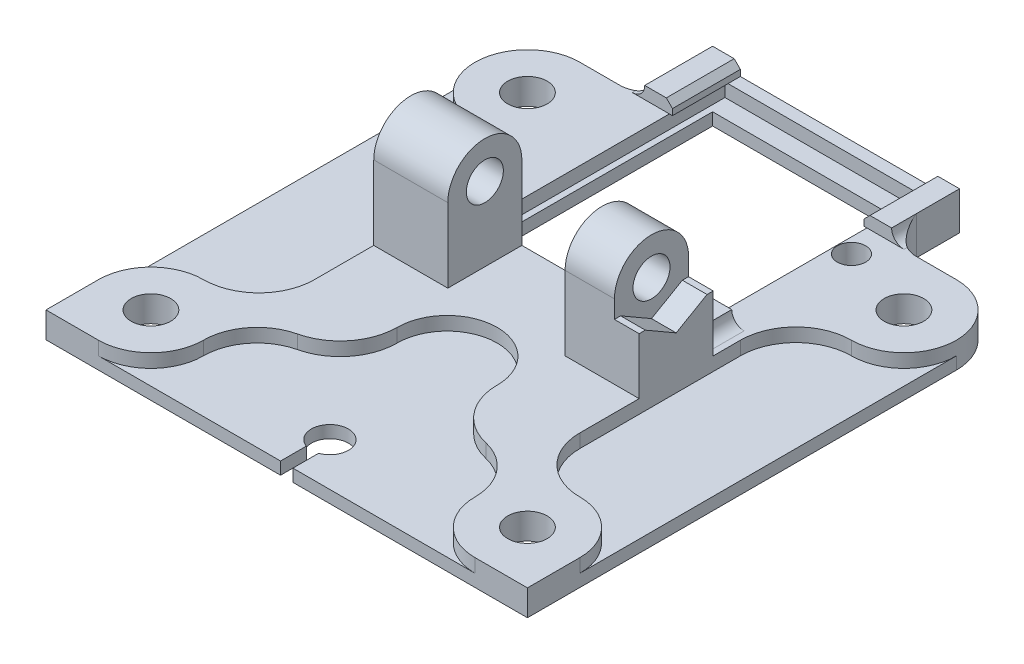
SolidWorks part; units mm, degrees
ref_plane "Front Plane" through (0, 0, 0) normal (0, 0, 1) x (1, 0, 0)
ref_plane "Top Plane" through (0, 0, 0) normal (0, 1, 0) x (1, 0, 0)
ref_plane "Right Plane" through (0, 0, 0) normal (1, 0, 0) x (0, 0, -1)
sketch "Sketch1" plane through (0, 0, 0) normal (0, 1, 0) x (1, 0, 0)
  line L0 (-19.5, 35.2) -> (-19.5, -19.5) construction
  line L1 (-19.5, 19.5) -> (19.5, 19.5)
  line L2 (-19.5, 19.5) -> (-19.5, -19.5)
  line L3 (-19.5, -19.5) -> (19.5, -19.5)
  line L4 (19.5, 19.5) -> (19.5, -19.5)
  line L5 (-19.5, 19.5) -> (19.5, -19.5) construction
  line L6 (-19.5, -19.5) -> (19.5, 19.5) construction
  line L7 (-19.5, -19.5) -> (19.5, -19.5) construction
  line L8 (0, -19.5) -> (0, 19.5) construction
  line L9 (-0.5, -19.5) -> (-0.5, -17.4142)
  line L10 (0.5, -19.5) -> (0.5, -17.4142)
  circle A0 centre (-15.25, -15.25) radius 1.6 construction
  circle A1 centre (15.25, -15.25) radius 1.6 construction
  circle A2 centre (9.2, 17.05) radius 1.15 construction
  circle A3 centre (15.25, 15.25) radius 1.6 construction
  circle A4 centre (-15.25, 15.25) radius 1.6 construction
  circle A5 centre (-15.25, -15.25) radius 1.6
  circle A6 centre (15.25, -15.25) radius 1.6
  circle A7 centre (9.2, 17.05) radius 1.15
  circle A8 centre (15.25, 15.25) radius 1.6
  circle A9 centre (-15.25, 15.25) radius 1.6
  circle A10 centre (-15.25, 15.25) radius 4.25
  circle A11 centre (15.25, 15.25) radius 4.25
  circle A12 centre (-15.25, -15.25) radius 4.25
  circle A13 centre (15.25, -15.25) radius 4.25
  circle A14 centre (0, -16) radius 1.5
  point P0 (0, 0)
  dimension "D1" = 3
  dimension "D2" = 3.5
  dimension "D3" = 1
extrude "Shape" add sketch "Sketch1" along normal blind 2.1 contours A13 L4 A11 L1 A10 L2 A12 L3 A7 | A10 A9 | A11 A8 | A13 A6 | A12 A5 | A12 L2 L3 | A13 L3 L4 region at (-0.0302, 0, -0.063) region at (-12.3298, 0, -18.1702) region at (18.1702, 0, -18.1702) region at (-18.5507, 0, 18.5507) region at (-15.25, 0, 11.1202) region at (18.1702, 0, 18.1702) region at (18.5507, 0, 18.5507)
sketch "Sketch3" plane through (0, 2.1, 0) normal (0, 1, 0) x (1, 0, 0)
  line L0 (0, 19.5) -> (0, -19.5) construction
  line L1 (-15.25, 19.5) -> (15.25, 19.5) construction
  line L3 (-19.5, 1.3) -> (19.5, 1.3) construction
  line L4 (-19.5, 15.25) -> (-19.5, -19.5) construction
  line L5 (19.5, 15.25) -> (19.5, -19.5) construction
  line L6 (4.75, 4.3) -> (10.75, 4.3)
  line L7 (-4.75, 4.3) -> (-10.75, 4.3)
  line L8 (-4.75, 4.3) -> (-4.75, -1.7)
  line L9 (-4.75, -1.7) -> (-10.75, -1.7)
  line L10 (-10.75, 4.3) -> (-10.75, -1.7)
  line L11 (-4.75, 4.3) -> (-10.75, -1.7) construction
  line L12 (-4.75, -1.7) -> (-10.75, 4.3) construction
  line L13 (4.75, 4.3) -> (4.75, -1.7)
  line L14 (4.75, -1.7) -> (10.75, -1.7)
  line L15 (10.75, 4.3) -> (10.75, -1.7)
  line L16 (-19.5, -19.5) -> (19.5, -19.5) construction
  line L18 (10.75, 4.3) -> (10.75, -1.7)
  point P12 (-7.75, 1.3)
  point P21 (0, 0)
  dimension "D1" = 18.2
  dimension "D2" = 9.5
  dimension "D3" = 6
  dimension "D4" = 6
extrude "Supports" add sketch "Sketch3" along normal blind 9 contours L7 L10 L9 L8 | L15 L6 L13 L14 region at (7.75, 2.1, -1.3) region at (-7.75, 2.1, -1.3)
sketch "Sketch4" plane through (-10.75, 0, 0) normal (-1, 0, 0) x (0, 0, 1)
  line L0 (-1.3, 11.1) -> (-1.3, 2.1) construction
  line L2 (-4.3, 2.1) -> (1.7, 2.1) construction
  line L3 (1.7, 11.1) -> (1.7, 2.1) construction
  line L4 (-4.3, 11.1) -> (1.7, 11.1) construction
  circle A0 centre (-1.3, 8.1) radius 3
  circle A1 centre (-1.3, 8.1) radius 1.5
  line M2 (1.7, 2.1) -> (1.7, 11.1)
  line M4 (-4.3, 11.1) -> (-4.3, 2.1)
  line M11 (1.7, 11.1) -> (-4.3, 11.1)
  dimension "D1" = 3
extrude "Support cuts" cut sketch "Sketch4" against normal up to surface (21.5 mm away) contours A1 L0 | L0 A1 | A0 M11 M4 | A0 M2 M11 region at (-10.75, 10.4299, 1.0299) region at (-10.75, 10.4299, -3.6299) region at (-10.75, 8.1, -0.6634) region at (-10.75, 8.1, -1.9366) up to face at (10.75, 6.6, -1.3)
sketch "Sketch5" plane through (10.75, 0, 0) normal (1, 0, 0) x (0, 0, -1)
  line L0 (-1.2, 6.6566) -> (-1.7, 6.6566)
  line L1 (1.3, 5.2132) -> (3.8, 6.6566)
  line L2 (3.8, 6.6566) -> (3.8, 9.5434)
  line L3 (3.8, 9.5434) -> (1.3, 10.9868)
  line L4 (1.3, 10.9868) -> (-1.2, 9.5434)
  line L5 (-1.2, 9.5434) -> (-1.2, 6.6566)
  line L6 (-1.2, 6.6566) -> (1.3, 5.2132)
  line L7 (3.8, 6.6566) -> (4.3, 6.6566)
  line L8 (4.3, 2.1) -> (-1.7, 2.1) construction
  line L9 (-1.7, 8.1) -> (-1.7, 2.1) construction
  line L10 (4.3, 8.1) -> (4.3, 2.1) construction
  line L12 (-1.7, 8.1) -> (-1.7, 2.1)
  line L13 (-1.7, 2.1) -> (4.3, 2.1)
  line L14 (4.3, 2.1) -> (4.3, 8.1)
  circle A0 centre (1.3, 8.1) radius 2.5 construction
  arc A2 (4.3, 8.1) -> (-1.7, 8.1) centre (1.3, 8.1) ccw construction
  arc A3 (4.3, 8.1) -> (-1.7, 8.1) centre (1.3, 8.1) ccw
  dimension "D1" = 5
extrude "Nut holder" cut sketch "Sketch5" against normal blind 2 contours L5 L6 L1 L2 L3 L4 | L2 L7 L0 L5 L4 L3 region at (10.75, 6.7313, 1.45) region at (10.75, 8.1, -1.3)
sketch "Sketch6" plane through (-10.75, 0, 0) normal (-1, 0, 0) x (0, 0, 1)
  circle A0 centre (-1.3, 8.1) radius 1.95
  dimension "D1" = 3.9
extrude "Screw cut" cut sketch "Sketch6" against normal offset from surface (3.5 mm away) 18 up to face at (10.75, 5.1485, -1.3)
sketch "Sketch9" plane through (0, 2.1, 0) normal (0, 1, 0) x (1, 0, 0)
  line L0 (8, 4.5) -> (8, 24) construction
  line L1 (8, 24) -> (-8, 24) construction
  line L2 (-8, 24) -> (-8, 4.5) construction
  line L3 (8, 4.5) -> (8, 24)
  line L4 (8, 24) -> (-8, 24)
  line L5 (-8, 24) -> (-8, 4.5)
  line L6 (-15.25, 19.5) -> (15.25, 19.5) construction
  line L7 (-15.25, 19.5) -> (15.25, 19.5)
  line L8 (-8, 24) -> (8, 19.5) construction
  line L9 (-8, 24) -> (8, 24)
  line L14 (10, 25) -> (-10, 25)
  line L15 (10, 25) -> (10, 18.5)
  line L16 (10, 18.5) -> (-10, 18.5)
  line L17 (-10, 25) -> (-10, 18.5)
  line L18 (10, 25) -> (-10, 18.5) construction
  line L19 (10, 18.5) -> (-10, 25) construction
  point P10 (0, 21.75)
  line M5 (15.25, 19.5) -> (-15.25, 19.5)
  dimension "D1" = 1
  dimension "D2" = 2
extrude "Datalogger front" add sketch "Sketch9" against normal up to surface (2.1 mm away) contours L4 L5 L3 M5 | L14 L17 L5 L4 L3 L7 L15 M5 region at (0, 2.1, -21.75) region at (8.2074, 2.1, -21.75) up to face at (0, 0, 3.8654)
sketch "Sketch10" plane through (0, 0, -25) normal (0, 0, -1) x (-1, 0, 0)
  line L1 (-8, 2.1) -> (8, 2.1)
  line L2 (-8, 2.1) -> (-8, 1)
  line L3 (-8, 1) -> (8, 1)
  line L4 (8, 2.1) -> (8, 1)
  line L6 (-8, 1) -> (8, 1) construction
  line L8 (8, 2.1) -> (8, 1) construction
extrude "Datalogger main cut" cut sketch "Sketch10" against normal offset from surface (20.7 mm away) 0.2 offset beyond the face yes
sketch "Sketch11" plane through (0, 1, 0) normal (0, 1, 0) x (1, 0, 0)
  line L6 (-7.5, 22.5) -> (7.5, 22.5)
  line L9 (8, 25) -> (-8, 25) construction
  line L12 (-7.5, 4.8) -> (7.5, 4.8)
  line L13 (7.5, 4.8) -> (7.5, 24.5)
  line L14 (7.5, 24.5) -> (-7.5, 24.5)
  line L15 (7.5, 24.5) -> (-7.5, 24.5)
  line L17 (-7.5, 24.5) -> (-7.5, 4.8)
  line L18 (-7.5, 4.8) -> (7.5, 4.8)
  line L19 (7.5, 4.8) -> (7.5, 24.5)
  line L23 (-7.5, 24.5) -> (-7.5, 4.8)
  dimension "D2" = 2.5
  dimension "D1" = 0.5
extrude "Datalogger bottom cut" cut sketch "Sketch11" against normal up to next contours L23 L18 L19 region at (0, 1, -13.65)
sketch "Sketch12" plane through (0, 1, 0) normal (0, 1, 0) x (1, 0, 0)
  line L1 (-8, 25) -> (8, 25)
  line L2 (-8, 25) -> (-8, 24)
  line L3 (-8, 24) -> (8, 24)
  line L4 (8, 25) -> (8, 24)
  dimension "D1" = 1
extrude "Datalogger front retainer" add sketch "Sketch12" along normal up to surface (1.1 mm away) up to face at (0, 2.1, -4.5902)
sketch "Sketch13" plane through (0, 2.1, 0) normal (0, 1, 0) x (1, 0, 0)
  line L1 (-8, 4.3) -> (-9.25, 4.3)
  line L2 (-8, 4.3) -> (-8, 7.3)
  line L3 (-8, 7.3) -> (-9.25, 7.3)
  line L4 (-9.25, 4.3) -> (-9.25, 7.3)
  line L5 (-8, 7.3) -> (-7.75, 7.3)
  line L6 (-8, 7.3) -> (-8, 4.3)
  line L7 (-8, 4.3) -> (-7.75, 4.3)
  line L8 (-7.75, 7.3) -> (-7.75, 4.3)
  line L9 (0, 7.608) -> (0, -4.6396) construction
  line L10 (9.25, 4.3) -> (9.25, 7.3)
  line L11 (8, 7.3) -> (9.25, 7.3)
  line L12 (8, 7.3) -> (7.75, 7.3)
  line L13 (7.75, 7.3) -> (7.75, 4.3)
  line L14 (8, 4.3) -> (7.75, 4.3)
  line L15 (8, 4.3) -> (9.25, 4.3)
  line M8 (8, 24) -> (8, 4.3)
  line M9 (8, 4.3) -> (10.75, 4.3)
  line M25 (-10.75, 4.3) -> (-8, 4.3)
  line M26 (-8, 4.3) -> (-8, 24)
  dimension "D1" = 1.5
  dimension "D2" = 3
  dimension "D3" = 0.25
extrude "Datalogger rear retainers" add sketch "Sketch13" along normal blind 1 contours L4 L3 M25 M26 | L8 L5 L7 M26 | L14 L12 L13 M8 | L11 L10 M8 M9 region at (-8.625, 2.1, -5.8) region at (-7.875, 2.1, -5.8) region at (8.625, 2.1, -5.8) region at (7.875, 2.1, -5.8)
sketch "Sketch14" plane through (0, 2.1, 0) normal (0, 1, 0) x (1, 0, 0)
  line L0 (-15.25, 19.5) -> (-10, 19.5) construction
  line L1 (-10, 25) -> (-7.75, 25)
  line L2 (-10, 25) -> (-10, 19.5)
  line L3 (-10, 19.5) -> (-7.75, 19.5)
  line L4 (-7.75, 25) -> (-7.75, 19.5)
  line L5 (-8, 4.3) -> (-8, 24) construction
  line L6 (-19.5, -19.5) -> (19.5, -19.5) construction
  line L8 (0, 25) -> (0, -19.5) construction
  line L9 (10, 25) -> (-10, 25) construction
  line L11 (10, 25) -> (10, 19.5)
  line L12 (10, 25) -> (7.75, 25)
  line L13 (7.75, 25) -> (7.75, 19.5)
  line L14 (10, 19.5) -> (7.75, 19.5)
  point P18 (0, 0)
  line M43 (10, 19.5) -> (10, 25)
  line M45 (10, 25) -> (-10, 25)
  line M46 (8, 24) -> (8, 7.3)
  line M68 (-8, 7.3) -> (-8, 24)
  line M71 (-10, 25) -> (-10, 19.5)
  line M161 (-8, 24) -> (8, 24)
  dimension "D1" = 0.25
extrude "Datalogger side retainers" add sketch "Sketch14" along normal up to surface (1 mm away) contours M45 M161 M46 M43 | M71 M68 M161 | L4 L3 M161 M68 | L14 L13 M46 M161 region at (-8.975, 2.1, -22.3) region at (-7.875, 2.1, -21.75) region at (8.975, 2.1, -22.3) region at (7.875, 2.1, -21.75) up to face at (-8.5, 3.1, -5.8)
sketch "Sketch15" plane through (0, 0, -25) normal (0, 0, -1) x (-1, 0, 0)
  line L0 (-7.75, 2.6) -> (-8.25, 3.1)
  line L2 (-7.75, 3.1) -> (-7.75, 2.1) construction
  line L3 (-8.25, 3.1) -> (-7.75, 3.1)
  line L4 (-7.75, 3.1) -> (-7.75, 2.6)
  line L5 (0, 0) -> (0, 2.1) construction
  line L6 (-7.75, 2.1) -> (7.75, 2.1) construction
  line L7 (8.25, 3.1) -> (7.75, 3.1)
  line L8 (7.75, 3.1) -> (7.75, 2.6)
  line L9 (7.75, 2.6) -> (8.25, 3.1)
  dimension "D1" = 45
extrude "Datalogger side retainer clips" cut sketch "Sketch15" against normal up to next
sketch "Sketch16" plane through (0, 2.1, 0) normal (0, 1, 0) x (1, 0, 0)
  line L0 (-19.5, 15.25) -> (-19.5, -19.5) construction
  line L1 (-15.25, 11) -> (-15.25, -11) construction
  line L2 (0, -2.4485) -> (-4.0515, -2.4485) construction
  line L3 (0, 25) -> (0, -19.5) construction
  line L4 (7.75, 25) -> (-7.75, 25) construction
  line L5 (-19.5, -19.5) -> (-0.5, -19.5) construction
  line L6 (-15.25, -11) -> (0, -11) construction
  line L7 (-11, -15.25) -> (0, -15.25) construction
  line L8 (-4.0515, 25) -> (-4.0515, -19.5) construction
  line L9 (-10.75, 4.3) -> (-10.75, -1.7) construction
  line L10 (-10.75, 6.5) -> (-10.75, 19.5) construction
  line L11 (-10, 19.5) -> (-8, 19.5) construction
  line L12 (-19.5, 15.25) -> (-19.5, -15.25)
  line L13 (-10.75, -1.7) -> (-10.75, -11) construction
  line L14 (-10.75, -6.5) -> (0, -6.5) construction
  line L15 (-15.25, 11) -> (-10.75, 11) construction
  line L16 (-10.75, 6.5) -> (-10.75, -6.5)
  line L17 (-4.75, -1.7) -> (-10.75, -1.7) construction
  line L18 (10.75, 6.5) -> (10.75, -6.5)
  line L19 (-15.25, -19.5) -> (15.25, -19.5)
  circle A0 centre (-15.25, 15.25) radius 4.25
  circle A1 centre (-15.25, -15.25) radius 4.25
  arc A2 (-15.25, 19.5) -> (-19.5, 15.25) centre (-15.25, 15.25) ccw construction
  arc A3 (-15.25, 11) -> (-10.75, 6.5) centre (-15.25, 6.5) cw
  arc A4 (-15.25, -11) -> (-10.75, -6.5) centre (-15.25, -6.5) ccw
  arc A5 (-11, -15.25) -> (-7.625, -11) centre (-6.6366, -15.25) cw
  arc A6 (-7.625, -11) -> (-4.0515, -6.5) centre (-8.6716, -6.5) ccw
  arc A7 (-4.0515, -6.5) -> (4.0515, -6.5) centre (0, -6.5) cw
  arc A8 (7.625, -11) -> (4.0515, -6.5) centre (8.6716, -6.5) cw
  arc A9 (11, -15.25) -> (7.625, -11) centre (6.6366, -15.25) ccw
  circle A10 centre (15.25, -15.25) radius 4.25
  arc A11 (15.25, -11) -> (10.75, -6.5) centre (15.25, -6.5) cw
  arc A12 (15.25, 11) -> (10.75, 6.5) centre (15.25, 6.5) ccw
  circle A13 centre (15.25, 15.25) radius 4.25
  point P57 (0, 0)
  point P58 (0, -19.5)
  line M39 (-19.5, 15.25) -> (-19.5, -19.5)
  line M40 (-19.5, -19.5) -> (-0.5, -19.5)
  line M41 (19.5, -19.5) -> (19.5, 15.25)
  arc M45 (-0.5, -17.4142) -> (0.5, -17.4142) centre (0, -16) cw
extrude "Weight cut" cut sketch "Sketch16" against normal offset from surface (1.1 mm away) 1 contours A1 A0 M39 | A10 A9 A8 A7 A6 A5 A1 M40 M45 | A13 L18 A10 M41 region at (-15.4165, 2.1, 0) region at (0, 2.1, 13.3087) region at (15.4165, 2.1, 0) up to face at (15.25, 0, 16.85)
fillet "Fillets" radius 2 2 edges at (10, 1.05, -19.5) (-10, 1.05, -19.5)
fillet "Fillet2" radius 1 4 edges at (10, 2.1, -20.5) (9.25, 2.1, -5.8) (-10, 2.1, -20.5) (-9.25, 2.1, -5.8)
